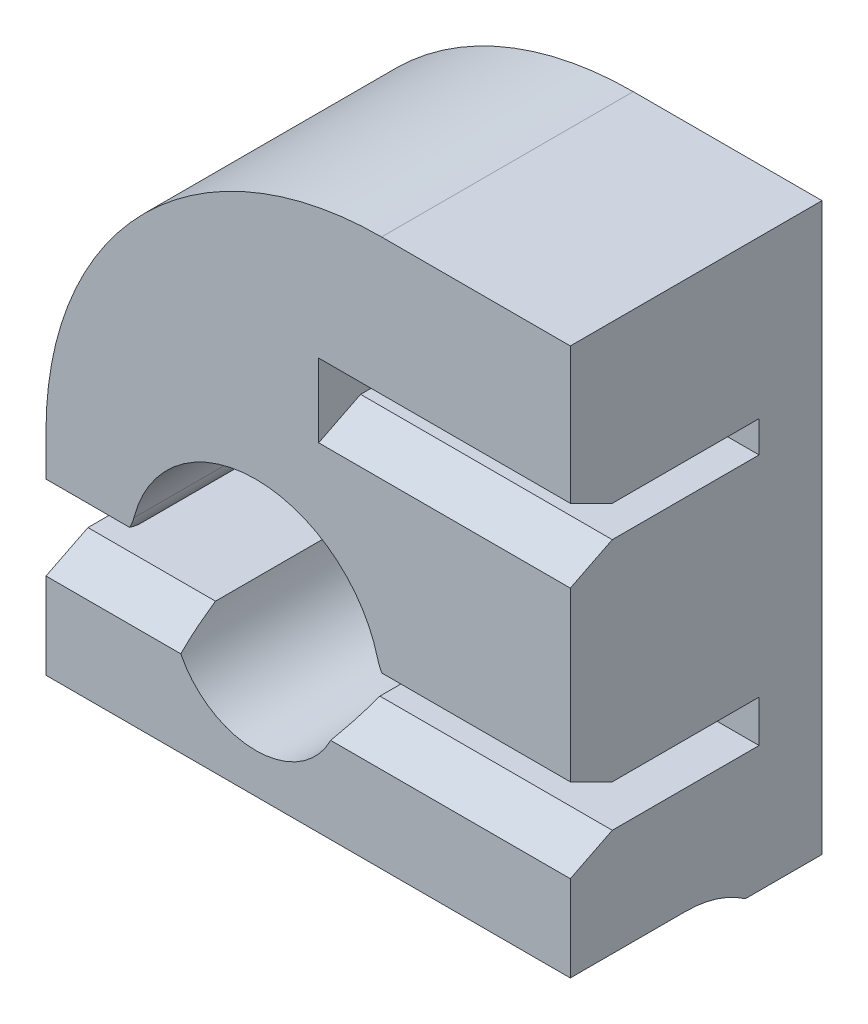
SolidWorks part; units mm, degrees
ref_plane "Front Plane" through (0, 0, 0) normal (0, 0, 1) x (1, 0, 0)
ref_plane "Top Plane" through (0, 0, 0) normal (0, 1, 0) x (1, 0, 0)
ref_plane "Right Plane" through (0, 0, 0) normal (1, 0, 0) x (0, 0, -1)
sketch "Sketch1" plane through (0, 0, 0) normal (0, 0, 1) x (1, 0, 0)
  line L1 (0, -6) -> (-25, -6)
  line L2 (0, -6) -> (0, 21)
  line L3 (0, 21) -> (-25, 21)
  line L4 (-25, -6) -> (-25, 21)
  dimension "D1" = 27
  dimension "D2" = 6
  dimension "D3" = 25
extrude "Boss-Extrude1" add sketch "Sketch1" along normal blind 12
sketch "Sketch2" plane through (0, 0, 12) normal (0, 0, 1) x (1, 0, 0)
  line L0 (-25, 21) -> (-25, -6) construction
  line L1 (0, 0) -> (-25, 0)
  line L2 (0, 0) -> (0, 2)
  line L3 (0, 2) -> (-9, 2)
  line L4 (-25, 0) -> (-25, 2)
  line L5 (0, -6) -> (0, 21) construction
  line L6 (0, 12) -> (-12, 12)
  line L7 (0, 12) -> (0, 13.5)
  line L8 (0, 13.5) -> (-1.5, 13.5)
  line L9 (-12, 12) -> (-12, 13.5)
  line L10 (-21, 2) -> (-25, 2)
  line L11 (-9.096, 13.5) -> (-8.596, 13)
  line L12 (-8.596, 13) -> (-8.096, 13)
  line L13 (-8.096, 13) -> (-7.596, 13.5)
  line L14 (-7.064, 13.5) -> (-6.564, 13)
  line L15 (-6.564, 13) -> (-6.064, 13)
  line L16 (-6.064, 13) -> (-5.564, 13.5)
  line L17 (-5.032, 13.5) -> (-4.532, 13)
  line L18 (-4.532, 13) -> (-4.032, 13)
  line L19 (-4.032, 13) -> (-3.532, 13.5)
  line L20 (-9.096, 13.5) -> (-12, 13.5)
  line L21 (-7.064, 13.5) -> (-7.596, 13.5)
  line L22 (-5.032, 13.5) -> (-5.564, 13.5)
  line L23 (-3, 13.5) -> (-2.5, 13)
  line L24 (-2.5, 13) -> (-2, 13)
  line L25 (-2, 13) -> (-1.5, 13.5)
  line L26 (-3, 13.5) -> (-3.532, 13.5)
  arc A0 (-9, 2) -> (-21, 2) centre (-15, 2) ccw
  dimension "D10" = 6
  dimension "D1" = 1.5
  dimension "D2" = 0.5
  dimension "D3" = 2.032
  dimension "D4" = 0.5
  dimension "D5" = 12
  dimension "D6" = 1.5
  dimension "D7" = 2
  dimension "D8" = 15
  dimension "D9" = 12
extrude "Cut-Extrude1" cut sketch "Sketch2" against normal offset from surface (9 mm away) 3 up to face at (-12.5, 7.5, 0)
sketch "Sketch3" plane through (0, 0, 0) normal (1, 0, 0) x (0, 0, -1)
  line L0 (-3, 0) -> (-12, 0) construction
  line L1 (-6.5, -5.1) -> (-14.9075, -5.1)
  line L2 (-3, 2) -> (-3, 0) construction
  line L3 (-6.5, -15) -> (-14.9075, -15)
  line L4 (-14.9075, -15) -> (-14.9075, -5.1)
  arc A0 (-6.5, -15) -> (-6.5, -5.1) centre (-6.5, -10.05) ccw
  dimension "D2" = 9.9
  dimension "D1" = 10.05
  dimension "D3" = 3.5
extrude "Cut-Extrude2" cut sketch "Sketch3" against normal through all
fillet "Fillet1" radius 16 1 edges at (-25, 21, 6)
chamfer "Chamfer2" distance 1 distance2 2 2 edges at (-23, 2, 12) (-4.5, 2, 12) first distance on face at (-7.4475, 12.1227, 12)
chamfer "Chamfer3" distance 1 distance2 2 1 edges at (-12.5, 0, 12) first distance on face at (-12.5, -2.55, 12)
ref_axis "Axis1" through (-15, 2, 3) along (0, 0, 1)
sketch "Sketch4" plane through (0, -6, 0) normal (0, -1, 0) x (1, 0, 0)
  line L0 (-15, 3) -> (-15, 12) construction
  line L1 (0, 3) -> (-25, 3) construction
  circle A0 centre (-15, 6.675) radius 1.6
  dimension "D2" = 3.2
  dimension "D1" = 3.675
extrude "Cut-Extrude3" [suppressed] cut sketch "Sketch4" against normal up to surface (6 mm away) contours A0
sketch "Sketch5" plane through (0, 0, 0) normal (1, 0, 0) x (0, 0, -1)
  line L0 (-12, 14.5) -> (-8.5, 12.75)
  line L1 (-12, 13.5) -> (-12, 21) construction
  line L2 (-3, 13.5) -> (-12, 13.5) construction
  line L3 (-10, 13.5) -> (-12, 13.5) construction
  line L4 (-12, 13.5) -> (-12, 14.5)
  line L5 (-12, 12) -> (-10, 12) construction
  line L6 (-3, 12) -> (-12, 12) construction
  line L7 (-8.5, 12.75) -> (-12, 11)
  line L8 (-12, 3) -> (-12, 12) construction
  line L9 (-12, 11) -> (-12, 12)
  line L10 (-10, 13.5) -> (-10, 12) construction
  line L11 (-12, 13.5) -> (-12, 12)
  dimension "D1" = 1
  dimension "D2" = 2
extrude "Cut-Extrude4" cut sketch "Sketch5" against normal up to surface (12 mm away) up to face at (-12, 12.75, 7.5)
fillet "Fillet2" radius 2 2 edges at (-9, 2, 6.5) (-21, 2, 6.5)
sketch "Sketch6" plane through (0, 0, 12) normal (0, 0, 1) x (1, 0, 0)
  circle A0 centre (-15, 0.7946) radius 4
  dimension "D1" = 8
extrude "Cut-Extrude5" cut sketch "Sketch6" against normal offset from surface (10 mm away) 1 up to face at (-13.75, 2.3547, 3) offset beyond the face yes
